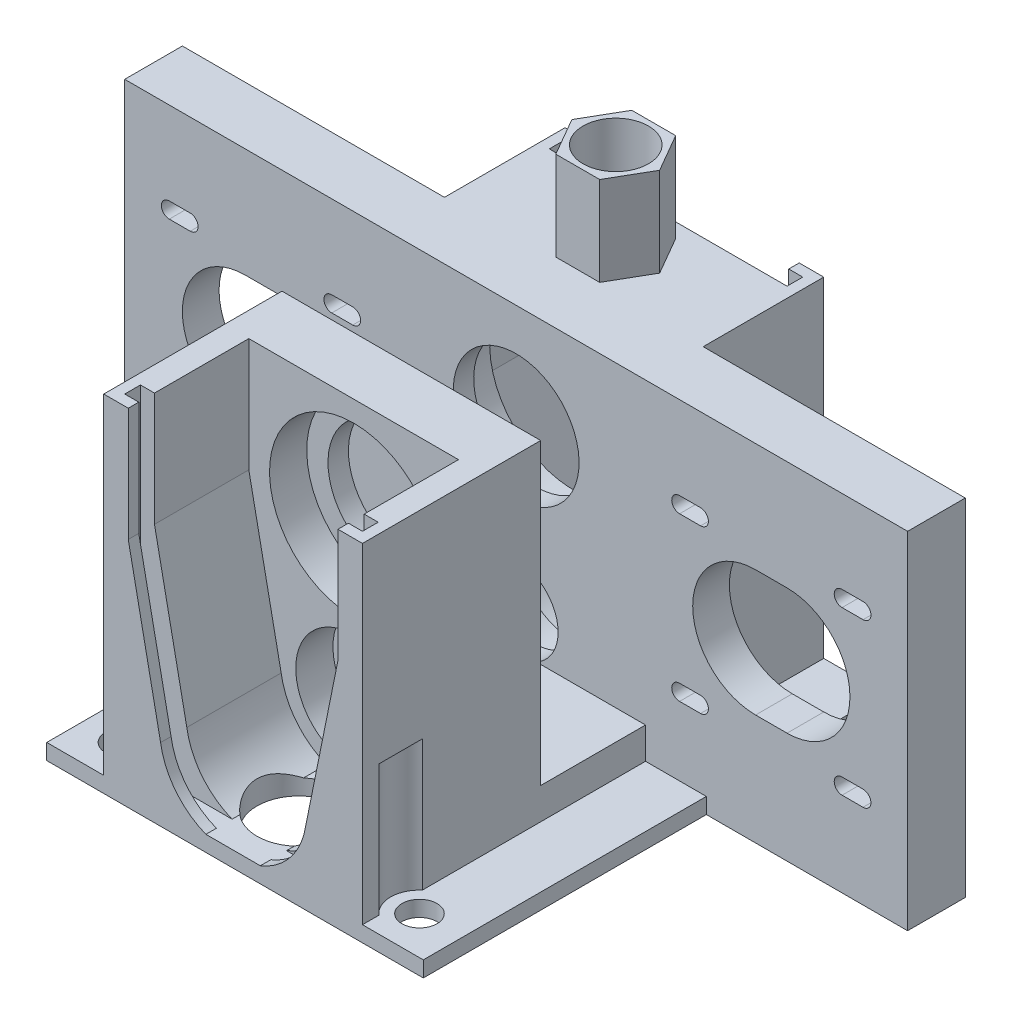
SolidWorks part; units mm, degrees
ref_plane "Front Plane" through (0, 0, 0) normal (0, 0, 1) x (1, 0, 0)
ref_plane "Top Plane" through (0, 0, 0) normal (0, 1, 0) x (1, 0, 0)
ref_plane "Right Plane" through (0, 0, 0) normal (1, 0, 0) x (0, 0, -1)
ref_axis "Axis1" through (88.99, 0, 0) along (-1, 0, 0)
ref_plane "Plane1" through (0, 0, 0) normal (0, 0, -1) x (-1, 0, 0)
ref_plane "Plane2" through (0, 0, 0) normal (0, -1, 0) x (-1, 0, 0)
ref_plane "Plane3" through (0, 0, -42) normal (0, 0, -1) x (-1, 0, 0)
sketch "Sketch2" plane through (0, 0, 0) normal (0, 0, -1) x (-1, 0, 0)
  line L2 (0, 58.0413) -> (0, 28.0413) construction
  line L3 (-24.6785, 78.0413) -> (24.6785, 78.0413)
  line L4 (57.5751, 12.0413) -> (-72.0682, 12.0413) construction
  line L5 (-24.6785, 78.0413) -> (-24.6785, 12.0413)
  line L6 (-24.6785, 12.0413) -> (24.6785, 12.0413)
  line L7 (24.6785, 12.0413) -> (24.6785, 78.0413)
  circle A0 centre (0, 28.0413) radius 11 construction
  circle A1 centre (0, 58.0413) radius 16 construction
  point P4 (0, 58.0413)
  point P6 (0, 28.0413)
  point P7 (20.0824, 64.1811)
  point P8 (15.3009, 32.7193)
  dimension "D1" = 32
  dimension "D2" = 22
  dimension "D6" = 66
  dimension "D3" = 30
  dimension "D5" = 20
  dimension "D4" = 16
extrude "Boss-Extrude1" add sketch "Sketch2" along normal blind 65
ref_plane "Plane5" through (0, 12.0413, 0) normal (0, -1, 0) x (-1, 0, 0)
sketch "Sketch3" plane through (0, 0, 0) normal (0, 0, -1) x (-1, 0, 0)
  line L0 (-24.6785, 12.0413) -> (24.6785, 12.0413) construction
  line L1 (0, 0) -> (0, 102.6324) construction
  circle A0 centre (0, 28.0413) radius 8
  circle A1 centre (0, 58.0413) radius 12
  circle A3 centre (0, 58.0413) radius 16 construction
  circle A4 centre (0, 28.0413) radius 11 construction
  dimension "D1" = 4
  dimension "D2" = 3
  dimension "D4" = 16
  dimension "D5" = 22
  dimension "D6" = 32
  dimension "D3" = 30
extrude "Cut-Extrude1" cut sketch "Sketch3" along normal blind 42
sketch "Sketch5" plane through (0, 0, -42) normal (0, 0, -1) x (-1, 0, 0)
  line L2 (-20, 76.0413) -> (20, 76.0413)
  line L4 (-24.6785, 12.0413) -> (24.6785, 12.0413) construction
  line L6 (13.8042, 25.708) -> (20, 49.5058)
  line L7 (-20, 49.5726) -> (-13.8042, 25.708)
  line L10 (24.6785, 78.0413) -> (-24.6785, 78.0413) construction
  line L11 (-20, 76.0413) -> (-20, 49.5726)
  line L12 (20, 76.0413) -> (20, 49.5058)
  circle A1 centre (0, 58.0413) radius 16 construction
  arc A3 (-13.8042, 25.708) -> (13.8042, 25.708) centre (0, 28.0413) ccw
  dimension "D2" = 16
  dimension "D1" = 14
  dimension "D6" = 32
  dimension "D5" = 2
  dimension "D7" = 30
  dimension "D8" = 20
  dimension "D9" = 20
extrude "Cut-Extrude2" cut sketch "Sketch5" along normal through all
sketch "Sketch6" plane through (0, 0, 0) normal (0, 0, -1) x (-1, 0, 0)
  circle A0 centre (0, 58.0413) radius 16.05
  circle A1 centre (0, 58.0413) radius 12 construction
  circle A2 centre (0, 28.0413) radius 11.05
  circle A3 centre (0, 28.0413) radius 8 construction
  dimension "D1" = 32.1
  dimension "D2" = 22.1
extrude "Cut-Extrude3" cut sketch "Sketch6" along normal blind 7.1
sketch "Sketch7" plane through (0, 0, -42) normal (0, 0, -1) x (-1, 0, 0)
  circle A2 centre (0, 58.0413) radius 16.05
  circle A3 centre (0, 58.0413) radius 16.05
  circle A5 centre (0, 28.0413) radius 11.05
  circle A6 centre (0, 28.0413) radius 11.05
  dimension "D1" = 0
  dimension "D2" = 0
extrude "Cut-Extrude4" cut sketch "Sketch7" against normal blind 7.1
sketch "Sketch8" plane through (0, 0, 0) normal (0, 0, -1) x (-1, 0, 0)
  line L2 (24.6785, 78.0413) -> (-24.6785, 78.0413)
  line L3 (24.6785, 78.0413) -> (24.6785, 12.0413)
  line L4 (24.6785, 12.0413) -> (-24.6785, 12.0413)
  line L5 (-24.6785, 12.0413) -> (-24.6785, 78.0413)
extrude "Boss-Extrude2" add sketch "Sketch8" against normal blind 23
sketch "Sketch9" plane through (0, 0, 0) normal (0, 0, -1) x (-1, 0, 0)
  line L2 (20, 78.0413) -> (-20, 78.0413)
  line L4 (-24.6785, 12.0413) -> (24.6785, 12.0413) construction
  line L5 (20, 78.0413) -> (20, 56.3516)
  line L6 (-20, 56.3516) -> (-13.8326, 25.8825)
  line L7 (13.8326, 25.8825) -> (20, 56.3516)
  line L8 (-20, 78.0413) -> (-20, 56.3516)
  circle A0 centre (0, 56.2822) radius 16 construction
  arc A3 (-13.8326, 25.8825) -> (13.8326, 25.8825) centre (0, 28.0413) ccw
  dimension "D1" = 14
  dimension "D5" = 32
  dimension "D2" = 16
  dimension "D6" = 20
  dimension "D7" = 20
extrude "Cut-Extrude5" cut sketch "Sketch9" against normal through all
ref_plane "Plane4" through (0, 0, -31) normal (0, 0, -1) x (-1, 0, 0)
sketch "Sketch10" plane through (0, 0, -31) normal (0, 0, -1) x (-1, 0, 0)
  line L1 (32.0175, 70.0413) -> (32.0175, 29.2185)
  line L2 (-24.6785, 12.0413) -> (24.6785, 12.0413) construction
  line L5 (-28.9461, 62.8412) -> (-28.9461, 21.0413)
  line L8 (0.9045, 21.0413) -> (-28.9461, 21.0413)
  line L9 (0, 0) -> (0, 85.4363) construction
  line L10 (0.9045, 21.0413) -> (32.0175, 29.2185)
  line L12 (-28.9461, 62.8412) -> (-28.9461, 84.6224)
  line L13 (-28.9461, 84.6224) -> (32.0175, 84.6224)
  line L14 (32.0175, 84.6224) -> (32.0175, 70.0413)
  circle A0 centre (0, 58.0413) radius 10 construction
  circle A1 centre (0, 58.0413) radius 16 construction
  circle A2 centre (0, 28.0413) radius 11 construction
  circle A4 centre (0, 28.0413) radius 4 construction
  dimension "D1" = 32
  dimension "D2" = 22
  dimension "D3" = 30
  dimension "D4" = 20
  dimension "D5" = 8
  dimension "D6" = 16
  dimension "D7" = 7
  dimension "D10" = 7
extrude "Cut-Extrude6" cut sketch "Sketch10" against normal blind 20
sketch "Sketch12" plane through (0, 0, 0) normal (0, 1, 0) x (1, 0, 0)
  circle A0 centre (0, -10.444) radius 8
  ellipse E0 centre (0, -2.444) end of major axis (14, -2.444) minor radius 1.2202 (13.8326, -2.2558) -> (-13.8326, -2.2558) ccw construction
  dimension "D1" = 16
  dimension "D2" = 8
extrude "Cut-Extrude8" cut sketch "Sketch12" along normal up to surface (14.0413 mm away) up to face at (0, 19.9619, 11.5)
sketch "Sketch13" plane through (0, 12.0413, 0) normal (0, -1, 0) x (-1, 0, 0)
  line L2 (24.6785, 11) -> (24.6785, 31)
  line L3 (24.6785, 11) -> (24.6785, 31) construction
  line L4 (24.6785, 31) -> (24.6785, 42)
  line L5 (-24.6785, 65) -> (24.6785, 65) construction
  line L7 (24.6785, 42) -> (74.6785, 42)
  line L8 (97.889, 42) -> (-97.889, 42) construction
  line L9 (74.6785, 42) -> (74.6785, 31)
  line L10 (97.889, 31) -> (-97.889, 31) construction
  line L11 (74.6785, 31) -> (24.6785, 31)
  line L12 (-24.6785, 42) -> (-74.6785, 42)
  line L13 (-24.6785, 65) -> (-24.6785, -23) construction
  line L14 (-74.6785, 42) -> (-74.6785, 31)
  line L15 (-74.6785, 31) -> (-24.6785, 31)
  line L16 (-24.6785, 31) -> (-24.6785, 42)
  dimension "D3" = 50
  dimension "D2" = 23
  dimension "D1" = 0
extrude "Boss-Extrude3" add sketch "Sketch13" against normal up to surface (66 mm away) up to face at (0, 78.0413, -48)
sketch "Sketch15" plane through (0, 0, -42) normal (0, 0, -1) x (-1, 0, 0)
  line L0 (0, 0) -> (0, 87.2744) construction
  line L1 (74.6785, 78.0413) -> (74.6785, 12.0413) construction
  line L2 (25.6785, 66.3413) -> (71.6785, 66.3413)
  line L3 (25.6785, 66.3413) -> (25.6785, 24.0413)
  line L4 (25.6785, 24.0413) -> (71.6785, 24.0413)
  line L5 (71.6785, 66.3413) -> (71.6785, 24.0413)
  line L6 (24.6785, 12.0413) -> (24.6785, 78.0413) construction
  line L7 (-27.1464, 12.0413) -> (27.1464, 12.0413) construction
  line L8 (-71.6785, 66.3413) -> (-71.6785, 24.0413)
  line L9 (-25.6785, 24.0413) -> (-71.6785, 24.0413)
  line L10 (-25.6785, 66.3413) -> (-25.6785, 24.0413)
  line L11 (-25.6785, 66.3413) -> (-71.6785, 66.3413)
  dimension "D1" = 3
  dimension "D2" = 1
  dimension "D3" = 42.3
  dimension "D4" = 12
extrude "Cut-Extrude9" cut sketch "Sketch15" against normal blind 4
sketch "Sketch16" plane through (0, 0, -42) normal (0, 0, -1) x (-1, 0, 0)
  line L0 (-105.1978, 45.1913) -> (88.1587, 45.1913) construction
  line L1 (71.6785, 66.3413) -> (25.6785, 66.3413) construction
  line L2 (25.6785, 24.0413) -> (71.6785, 24.0413) construction
  line L3 (45.6785, 45.1913) -> (51.6785, 45.1913) construction
  line L4 (45.6785, 57.1913) -> (51.6785, 57.1913)
  line L5 (45.6785, 33.1913) -> (51.6785, 33.1913)
  line L6 (48.6785, 83.554) -> (48.6785, 16.5047) construction
  line L7 (25.6785, 66.3413) -> (25.6785, 24.0413) construction
  line L8 (71.6785, 24.0413) -> (71.6785, 66.3413) construction
  line L9 (31.1785, 60.6913) -> (35.1785, 60.6913) construction
  line L10 (31.1785, 62.1913) -> (35.1785, 62.1913)
  line L11 (31.1785, 59.1913) -> (35.1785, 59.1913)
  line L12 (66.1785, 60.6913) -> (62.1785, 60.6913) construction
  line L25 (66.1785, 62.1913) -> (62.1785, 62.1913)
  line L26 (66.1785, 59.1913) -> (62.1785, 59.1913)
  line L27 (31.1785, 29.6913) -> (35.1785, 29.6913) construction
  line L28 (31.1785, 28.1913) -> (35.1785, 28.1913)
  line L29 (31.1785, 31.1913) -> (35.1785, 31.1913)
  line L30 (66.1785, 29.6913) -> (62.1785, 29.6913) construction
  line L31 (66.1785, 28.1913) -> (62.1785, 28.1913)
  line L32 (66.1785, 31.1913) -> (62.1785, 31.1913)
  line L33 (0, 0) -> (0, 89.9864) construction
  line L34 (-45.6785, 45.1913) -> (-51.6785, 45.1913) construction
  line L35 (-45.6785, 57.1913) -> (-51.6785, 57.1913)
  line L36 (-45.6785, 33.1913) -> (-51.6785, 33.1913)
  line L37 (-31.1785, 60.6913) -> (-35.1785, 60.6913) construction
  line L38 (-31.1785, 62.1913) -> (-35.1785, 62.1913)
  line L39 (-31.1785, 59.1913) -> (-35.1785, 59.1913)
  line L40 (-66.1785, 60.6913) -> (-62.1785, 60.6913) construction
  line L41 (-66.1785, 62.1913) -> (-62.1785, 62.1913)
  line L42 (-66.1785, 59.1913) -> (-62.1785, 59.1913)
  line L43 (-31.1785, 29.6913) -> (-35.1785, 29.6913) construction
  line L44 (-31.1785, 28.1913) -> (-35.1785, 28.1913)
  line L45 (-31.1785, 31.1913) -> (-35.1785, 31.1913)
  line L46 (-66.1785, 29.6913) -> (-62.1785, 29.6913) construction
  line L47 (-66.1785, 28.1913) -> (-62.1785, 28.1913)
  line L48 (-66.1785, 31.1913) -> (-62.1785, 31.1913)
  arc A0 (45.6785, 57.1913) -> (45.6785, 33.1913) centre (45.6785, 45.1913) ccw
  arc A1 (51.6785, 33.1913) -> (51.6785, 57.1913) centre (51.6785, 45.1913) ccw
  arc A2 (31.1785, 62.1913) -> (31.1785, 59.1913) centre (31.1785, 60.6913) ccw
  arc A3 (35.1785, 59.1913) -> (35.1785, 62.1913) centre (35.1785, 60.6913) ccw
  arc A16 (66.1785, 62.1913) -> (66.1785, 59.1913) centre (66.1785, 60.6913) cw
  arc A17 (62.1785, 59.1913) -> (62.1785, 62.1913) centre (62.1785, 60.6913) cw
  arc A18 (31.1785, 28.1913) -> (31.1785, 31.1913) centre (31.1785, 29.6913) cw
  arc A19 (35.1785, 31.1913) -> (35.1785, 28.1913) centre (35.1785, 29.6913) cw
  arc A20 (66.1785, 28.1913) -> (66.1785, 31.1913) centre (66.1785, 29.6913) ccw
  arc A21 (62.1785, 31.1913) -> (62.1785, 28.1913) centre (62.1785, 29.6913) ccw
  arc A22 (-45.6785, 57.1913) -> (-45.6785, 33.1913) centre (-45.6785, 45.1913) cw
  arc A23 (-51.6785, 33.1913) -> (-51.6785, 57.1913) centre (-51.6785, 45.1913) cw
  arc A24 (-31.1785, 62.1913) -> (-31.1785, 59.1913) centre (-31.1785, 60.6913) cw
  arc A25 (-35.1785, 59.1913) -> (-35.1785, 62.1913) centre (-35.1785, 60.6913) cw
  arc A26 (-66.1785, 62.1913) -> (-66.1785, 59.1913) centre (-66.1785, 60.6913) ccw
  arc A27 (-62.1785, 59.1913) -> (-62.1785, 62.1913) centre (-62.1785, 60.6913) ccw
  arc A28 (-31.1785, 28.1913) -> (-31.1785, 31.1913) centre (-31.1785, 29.6913) ccw
  arc A29 (-35.1785, 31.1913) -> (-35.1785, 28.1913) centre (-35.1785, 29.6913) ccw
  arc A30 (-66.1785, 28.1913) -> (-66.1785, 31.1913) centre (-66.1785, 29.6913) cw
  arc A31 (-62.1785, 31.1913) -> (-62.1785, 28.1913) centre (-62.1785, 29.6913) cw
  point P8 (48.6785, 45.1913)
  point P14 (33.1785, 60.6913)
  point P28 (64.1785, 60.6913)
  point P36 (33.1785, 29.6913)
  point P43 (64.1785, 29.6913)
  point P52 (-48.6785, 45.1913)
  point P59 (-33.1785, 60.6913)
  point P66 (-64.1785, 60.6913)
  point P73 (-33.1785, 29.6913)
  point P80 (-64.1785, 29.6913)
  dimension "D1" = 12
  dimension "D3" = 31
  dimension "D4" = 1.5
  dimension "D2" = 31
  dimension "D5" = 4
  dimension "D6" = 6
extrude "Cut-Extrude10" cut sketch "Sketch16" against normal up to next
sketch "Sketch17" plane through (0, 78.0413, 0) normal (0, 1, 0) x (1, 0, 0)
  line L0 (0, 55.3583) -> (0, 85.749) construction
  line L1 (-35.5458, 50) -> (45.8299, 50) construction
  line L4 (97.889, 42) -> (-97.889, 42) construction
  line L5 (8.3716, 50) -> (4.1858, 57.25)
  line L6 (4.1858, 57.25) -> (-4.1858, 57.25)
  line L7 (-4.1858, 57.25) -> (-8.3716, 50)
  line L8 (-8.3716, 50) -> (-4.1858, 42.75)
  line L9 (-4.1858, 42.75) -> (4.1858, 42.75)
  line L10 (4.1858, 42.75) -> (8.3716, 50)
  circle A0 centre (0, 50) radius 7.25 construction
  circle A1 centre (0, 50) radius 6.25
  dimension "D2" = 12.5
  dimension "D1" = 14.5
  dimension "D3" = 8
extrude "Boss-Extrude4" add sketch "Sketch17" along normal blind 17
sketch "Sketch18" plane through (0, 78.0413, 0) normal (0, 1, 0) x (1, 0, 0)
  circle A2 centre (0, 50) radius 6.25
  circle A3 centre (0, 50) radius 6.25
  dimension "D1" = 0
extrude "Cut-Extrude11" cut sketch "Sketch18" against normal up to next
sketch "Sketch19" plane through (0, 12.0413, 0) normal (0, -1, 0) x (-1, 0, 0)
  line L0 (-66.3049, 12.556) -> (66.3049, 12.556) construction
  line L1 (0, 76.6155) -> (0, 65) construction
  line L2 (-61.7241, 74.2802) -> (0.6987, 11.8573) construction
  line L4 (13.4481, 26.0042) -> (0, 12.556) construction
  line L7 (-36.2843, 48.8403) -> (-36.2843, -23)
  line L9 (35.556, 48.8403) -> (35.556, -23)
  line L10 (-36.2843, 48.8403) -> (-36.2843, 65)
  line L12 (35.556, 65) -> (35.556, 48.8403)
  line L27 (0, 42) -> (0, -57.588) construction
  line L28 (-25.9179, -13.3619) -> (-763.264, -750.708) construction
  line L29 (-36.2843, 65) -> (35.556, 65)
  line L30 (-36.2843, -23) -> (35.556, -23)
  circle A3 centre (-28.2843, 40.8403) radius 3.3465
  circle A6 centre (28.2843, 40.8403) radius 3.3465
  circle A7 centre (-28.2843, -15.7282) radius 3.3465
  circle A8 centre (28.2843, -15.7282) radius 3.3465
  circle A10 centre (0, -10.444) radius 8
  circle A11 centre (0, -10.444) radius 8
  point P3 (0, 12.556)
  dimension "D4" = 88
  dimension "D2" = 45
  dimension "D1" = 45
  dimension "D5" = 40
  dimension "D6" = 8
  dimension "D7" = 71.8403
  dimension "D3" = 0
extrude "Boss-Extrude5" add sketch "Sketch19" against normal blind 3
sketch "Sketch20" plane through (0, 15.0413, 0) normal (0, 1, 0) x (1, 0, 0)
  circle A0 centre (-28.2843, -15.7282) radius 5.5
  circle A1 centre (28.2843, -15.7282) radius 5.5
  circle A2 centre (28.2843, 40.8403) radius 5.5
  circle A3 centre (-28.2843, 40.8403) radius 5.5
  dimension "D1" = 11
extrude "Cut-Extrude12" cut sketch "Sketch20" along normal blind 25
sketch "Sketch21" plane through (0, 12.0413, 0) normal (0, -1, 0) x (-1, 0, 0)
  circle A0 centre (-28.2843, 40.8403) radius 3.3465
  arc A1 (-25.1451, 42) -> (-31.4234, 42) centre (-28.2843, 40.8403) ccw construction
  circle A2 centre (28.2843, 40.8403) radius 3.3465
  arc A3 (31.4234, 42) -> (25.1451, 42) centre (28.2843, 40.8403) ccw construction
extrude "Cut-Extrude13" cut sketch "Sketch21" against normal up to next
sketch "Sketch22" plane through (0, 0, 0) normal (1, 0, 0) x (0, 0, -1)
  line L0 (63, 78.0413) -> (63, 15.0413)
  line L3 (65, 78.0413) -> (42, 78.0413) construction
  line L7 (44.9934, 15.0413) -> (65, 15.0413) construction
  line L8 (63, 15.0413) -> (65, 15.0413)
  line L9 (65, 78.0413) -> (65, 15.0413) construction
  line L10 (-21, 81.0679) -> (-21, 15.0413)
  line L12 (-23, 15.0413) -> (-19.8814, 15.0413) construction
  line L13 (-21, 15.0413) -> (-23, 15.0413)
  line L14 (-23, 78.0413) -> (-23, 15.0413) construction
  dimension "D1" = 2
  dimension "D2" = 2
sketch "Sketch23" plane through (0, 78.0413, 0) normal (0, 1, 0) x (1, 0, 0)
  line L0 (-24.6785, 65) -> (24.6785, 65) construction
  line L1 (-22.6785, 63) -> (22.6785, 63)
  line L2 (-22.6785, 63) -> (-22.6785, 60)
  line L3 (-22.6785, 60) -> (22.6785, 60)
  line L4 (22.6785, 63) -> (22.6785, 60)
  line L5 (-24.6785, 65) -> (-24.6785, 44.9934) construction
  line L6 (24.6785, 44.9934) -> (24.6785, 65) construction
  line L8 (-22.6785, -18) -> (22.6785, -18)
  line L9 (-22.6785, -18) -> (-22.6785, -21)
  line L10 (-22.6785, -21) -> (22.6785, -21)
  line L11 (22.6785, -18) -> (22.6785, -21)
  line L12 (-24.6785, 11) -> (-24.6785, -23) construction
  line L13 (24.6785, 11) -> (24.6785, -23) construction
  line L14 (5.1962, -23) -> (-5.1962, -23) construction
  point P20 (22.6785, -19.5)
  dimension "D1" = 2
  dimension "D2" = 2
  dimension "D3" = 2
  dimension "D4" = 3
  dimension "D5" = 2
  dimension "D6" = 3
  dimension "D7" = 2
  dimension "D8" = 2
  dimension "D9" = 45.357
  dimension "D10" = 45.357
extrude "Cut-Extrude14" cut sketch "Sketch23" against normal up to surface (63 mm away) up to face at (-27.9886, 15.0413, 2.5761)
sketch "Sketch24" plane through (0, 0, -65) normal (0, 0, -1) x (-1, 0, 0)
  line L0 (24.6785, 78.0413) -> (-24.6785, 78.0413) construction
  line L1 (-20, 76.0413) -> (20, 76.0413)
  line L2 (-20, 76.0413) -> (-20, 78.0413)
  line L3 (-20, 78.0413) -> (20, 78.0413)
  line L4 (20, 76.0413) -> (20, 78.0413)
extrude "Cut-Extrude15" cut sketch "Sketch24" against normal up to next
